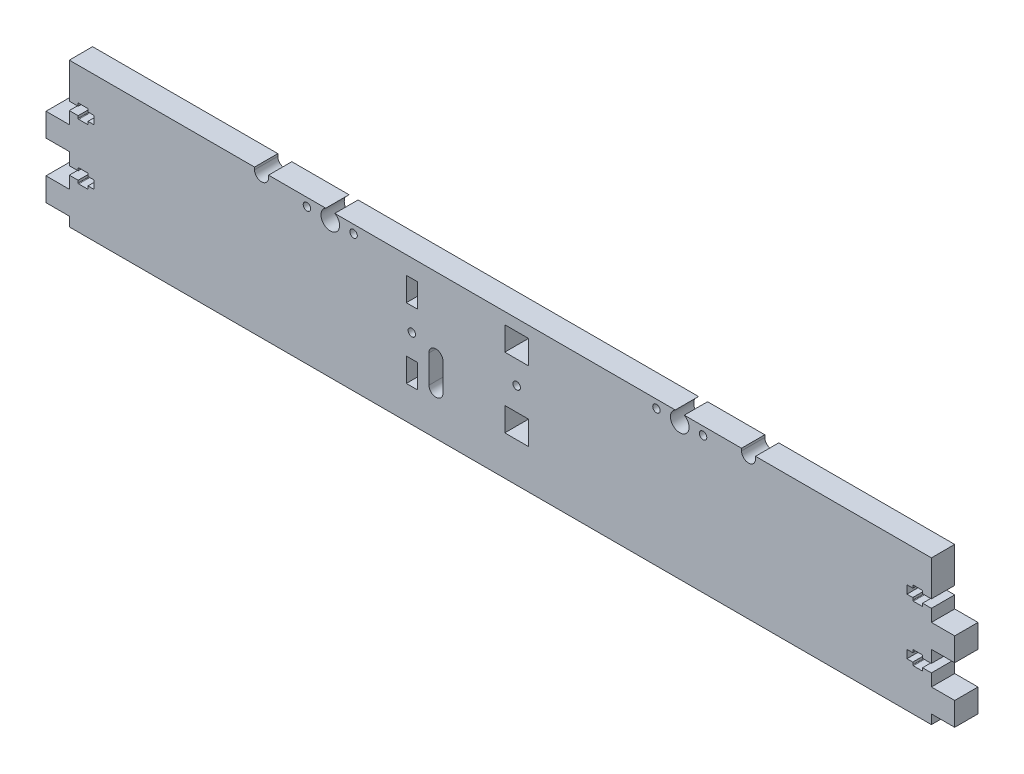
SolidWorks part; units mm, degrees
ref_plane "Front Plane" through (0, 0, 0) normal (0, 0, 1) x (1, 0, 0)
ref_plane "Top Plane" through (0, 0, 0) normal (0, 1, 0) x (1, 0, 0)
ref_plane "Right Plane" through (0, 0, 0) normal (1, 0, 0) x (0, 0, -1)
sketch "Sketch1" plane through (0, 0, 0) normal (0, 0, 1) x (1, 0, 0)
  line L0 (0, 0) -> (-185, 0)
  line L1 (-185, 0) -> (-185, -62) construction
  line L2 (0, -62) -> (-185, -62)
  line L3 (-185, -62) -> (-185, -58)
  line L4 (-185, -58) -> (-195, -58)
  line L5 (-195, -58) -> (-195, -48)
  line L6 (-195, -48) -> (-185, -48)
  line L7 (-185, -48) -> (-185, -34)
  line L8 (-185, -34) -> (-195, -34)
  line L9 (-195, -34) -> (-195, -24)
  line L10 (-195, -24) -> (-185, -24)
  line L11 (0, -62) -> (0, 0)
  line L12 (-185, -24) -> (-185, 0)
  line L13 (-195, -58) -> (-195, -24) construction
  line L14 (-195, -29) -> (-185, -29) construction
  line L15 (-195, -53) -> (-185, -53) construction
  dimension "D3" = 10
  dimension "D1" = 185
  dimension "D2" = 10
  dimension "D4" = 10
  dimension "D5" = 24
  dimension "D6" = 29
  dimension "D7" = 62
extrude "MainBody" add sketch "Sketch1" along normal blind 10
sketch "Sketch3" plane through (0, 0, 10) normal (0, 0, 1) x (1, 0, 0)
  line L0 (-185, -17) -> (-174.5, -17) construction
  line L1 (-185, 0) -> (-185, -24) construction
  line L2 (-185, -18.75) -> (-181.2, -18.75)
  line L3 (-181.2, -18.75) -> (-181.2, -19.75)
  line L4 (-180.95, -20) -> (-177.25, -20)
  line L5 (-177, -19.75) -> (-177, -18.75)
  line L6 (-177, -18.75) -> (-174.5, -18.75)
  line L7 (-174.5, -18.75) -> (-174.5, -15.25)
  line L8 (-181.2, -18.75) -> (-177, -18.75) construction
  line L9 (-195, -24) -> (-195, -34) construction
  line L10 (-181.2, -15.25) -> (-177, -15.25) construction
  line L11 (-177, -15.25) -> (-174.5, -15.25)
  line L12 (-177, -14.25) -> (-177, -15.25)
  line L13 (-180.95, -14) -> (-177.25, -14)
  line L14 (-181.2, -15.25) -> (-181.2, -14.25)
  line L15 (-185, -15.25) -> (-181.2, -15.25)
  line L16 (-185, -18.75) -> (-185, -15.25)
  line L17 (-185, -24) -> (-185, -34) construction
  line L19 (-195, -24) -> (-195, -34) construction
  line L20 (-195, -29) -> (-185, -29) construction
  line L21 (-181.2, -42.75) -> (-177, -42.75) construction
  line L22 (-181.2, -39.25) -> (-177, -39.25) construction
  line L23 (-185, -41) -> (-174.5, -41) construction
  line L24 (-185, -39.25) -> (-185, -42.75)
  line L25 (-185, -42.75) -> (-181.2, -42.75)
  line L26 (-181.2, -42.75) -> (-181.2, -43.75)
  line L27 (-180.95, -44) -> (-177.25, -44)
  line L28 (-177, -43.75) -> (-177, -42.75)
  line L29 (-177, -42.75) -> (-174.5, -42.75)
  line L30 (-174.5, -39.25) -> (-174.5, -42.75)
  line L31 (-177, -39.25) -> (-174.5, -39.25)
  line L32 (-177, -38.25) -> (-177, -39.25)
  line L33 (-180.95, -38) -> (-177.25, -38)
  line L34 (-181.2, -39.25) -> (-181.2, -38.25)
  line L35 (-185, -39.25) -> (-181.2, -39.25)
  line L36 (-181.2, -15.25) -> (-177, -15.25) construction
  arc A0 (-177.25, -20) -> (-177, -19.75) centre (-177.25, -19.75) ccw
  arc A1 (-181.2, -19.75) -> (-180.95, -20) centre (-180.95, -19.75) ccw
  arc A2 (-181.2, -14.25) -> (-180.95, -14) centre (-180.95, -14.25) cw
  arc A3 (-177.25, -14) -> (-177, -14.25) centre (-177.25, -14.25) cw
  arc A4 (-177.25, -44) -> (-177, -43.75) centre (-177.25, -43.75) ccw
  arc A5 (-181.2, -43.75) -> (-180.95, -44) centre (-180.95, -43.75) ccw
  arc A6 (-181.2, -38.25) -> (-180.95, -38) centre (-180.95, -38.25) cw
  arc A7 (-177.25, -38) -> (-177, -38.25) centre (-177.25, -38.25) cw
  point P6 (-195, -29)
  point P15 (-177, -20)
  point P18 (-181.2, -20)
  point P29 (-181.2, -14)
  point P30 (-177, -14)
  point P62 (-177, -44)
  point P63 (-181.2, -44)
  point P64 (-181.2, -38)
  point P65 (-177, -38)
  dimension "D2" = 8
  dimension "D7" = 0.25
  dimension "D1" = 10.5
  dimension "D3" = 1.75
  dimension "D4" = 3
  dimension "D5" = 12
  dimension "D6" = 4.2
extrude "ScrewCutouts" cut sketch "Sketch3" against normal through all
mirror "Mirror1" about plane through (0, 0, 0) normal (1, 0, 0) of "ScrewCutouts", "MainBody"
sketch "Sketch2" plane through (0, 0, 10) normal (0, 0, 1) x (1, 0, 0)
  line L0 (0, 0) -> (0, -62) construction
  line L1 (-185, -62) -> (185, -62) construction
  line L2 (2, 0) -> (2, -62) construction
  line L3 (185, 0) -> (-185, 0) construction
  line L4 (-63, -3.5) -> (-83, -3.5) construction
  line L5 (-73, -7.5) -> (-73, 0.5) construction
  line L6 (77, -7.5) -> (77, 0.5) construction
  line L7 (67, -3.5) -> (87, -3.5) construction
  circle A0 centre (-73, -3.5) radius 4
  circle A1 centre (-83, -3.5) radius 1.6
  circle A2 centre (-63, -3.5) radius 1.6
  circle A3 centre (67, -3.5) radius 1.6
  circle A4 centre (87, -3.5) radius 1.6
  circle A5 centre (77, -3.5) radius 4
  dimension "D1" = 3.2
  dimension "D2" = 8
  dimension "D3" = 10
  dimension "D4" = 3.5
  dimension "D5" = 75
  dimension "D6" = 2
extrude "RodCutouts" cut sketch "Sketch2" against normal through all
sketch "Sketch4" plane through (0, 0, 10) normal (0, 0, 1) x (1, 0, 0)
  line L0 (77, -3.5) -> (-73, -3.5) construction
  line L1 (2, -3.5) -> (2, -62) construction
  line L2 (-185, -62) -> (185, -62) construction
  line L3 (7, -45.1) -> (7, -4.9) construction
  line L4 (75.0635, 0) -> (-71.0635, 0) construction
  line L5 (7, -10) -> (7, -40) construction
  line L6 (1.9, -4.9) -> (12.1, -4.9)
  line L7 (1.9, -4.9) -> (1.9, -15.1)
  line L8 (1.9, -15.1) -> (12.1, -15.1)
  line L9 (12.1, -4.9) -> (12.1, -15.1)
  line L10 (1.9, -4.9) -> (12.1, -15.1) construction
  line L11 (1.9, -15.1) -> (12.1, -4.9) construction
  line L12 (1.9, -34.9) -> (12.1, -34.9)
  line L13 (1.9, -34.9) -> (1.9, -45.1)
  line L14 (1.9, -45.1) -> (12.1, -45.1)
  line L15 (12.1, -34.9) -> (12.1, -45.1)
  line L16 (1.9, -34.9) -> (12.1, -45.1) construction
  line L17 (1.9, -45.1) -> (12.1, -34.9) construction
  circle A0 centre (7, -25) radius 1.6
  point P12 (7, -10)
  point P17 (7, -40)
  dimension "D8" = 3.2
  dimension "D1" = 10.2
  dimension "D2" = 10.2
  dimension "D3" = 10.2
  dimension "D4" = 10.2
  dimension "D5" = 30
  dimension "D6" = 10
  dimension "D7" = 5
extrude "Cut-Extrude3" cut sketch "Sketch4" against normal through all
sketch "Sketch5" plane through (0, 0, 10) normal (0, 0, 1) x (1, 0, 0)
  line L0 (-38, 0) -> (-38, -62) construction
  line L1 (-74.9365, 0) -> (-185, 0) construction
  line L2 (-185, -62) -> (185, -62) construction
  line L3 (-40.35, -17.85) -> (-40.35, -37.65) construction
  line L4 (-40.35, -7.65) -> (-35.65, -7.65)
  line L5 (-40.35, -7.65) -> (-40.35, -17.85)
  line L6 (-40.35, -17.85) -> (-35.65, -17.85)
  line L7 (-35.65, -7.65) -> (-35.65, -17.85)
  line L8 (-40.35, -7.65) -> (-35.65, -17.85) construction
  line L9 (-40.35, -17.85) -> (-35.65, -7.65) construction
  line L10 (-40.35, -37.65) -> (-35.65, -37.65)
  line L11 (-40.35, -37.65) -> (-40.35, -47.85)
  line L12 (-40.35, -47.85) -> (-35.65, -47.85)
  line L13 (-35.65, -37.65) -> (-35.65, -47.85)
  line L14 (-40.35, -37.65) -> (-35.65, -47.85) construction
  line L15 (-40.35, -47.85) -> (-35.65, -37.65) construction
  line L16 (-35.65, -37.65) -> (-35.65, -17.85) construction
  line L17 (-40.35, -27.75) -> (-35.65, -27.75) construction
  line L18 (-73, -3.5) -> (77, -3.5) construction
  line L19 (2, -3.5) -> (2, -62) construction
  line L20 (2, -32.75) -> (-195, -32.75) construction
  line L21 (-195, -24) -> (-195, -34) construction
  circle A0 centre (-38, -27.75) radius 1.6
  point P6 (-38, -12.75)
  point P11 (-38, -42.75)
  dimension "D3" = 10.2
  dimension "D4" = 10.2
  dimension "D5" = 30
  dimension "D6" = 3.2
  dimension "D1" = 4.7
  dimension "D2" = 0
  dimension "D7" = 40
  dimension "D8" = 5
extrude "EndstopHolder" cut sketch "Sketch5" against normal through all
sketch "Sketch6" plane through (0, 0, 10) normal (0, 0, 1) x (1, 0, 0)
  line L0 (-40.35, -37.65) -> (-40.35, -17.85) construction
  line L1 (-42.35, -37.65) -> (-27.65, -37.65) construction
  line L3 (-27.65, -43.65) -> (-27.65, -31.65) construction
  line L4 (-30.65, -43.65) -> (-30.65, -31.65)
  line L5 (-24.65, -43.65) -> (-24.65, -31.65)
  line L6 (-35.65, -37.65) -> (-40.35, -37.65) construction
  line L7 (-35.65, -47.85) -> (-35.65, -37.65) construction
  arc A0 (-30.65, -43.65) -> (-24.65, -43.65) centre (-27.65, -43.65) ccw
  arc A1 (-24.65, -31.65) -> (-30.65, -31.65) centre (-27.65, -31.65) ccw
  point P10 (-27.65, -37.65)
  dimension "D1" = 3
  dimension "D2" = 12
  dimension "D3" = 8
  dimension "D4" = 0
extrude "EndstopWires" cut sketch "Sketch6" against normal through all
sketch "Sketch7" plane through (0, 0, 10) normal (0, 0, 1) x (1, 0, 0)
  line L0 (-73, -3.5) -> (77, -3.5) construction
  line L1 (2, -3.5) -> (2, -62) construction
  line L3 (-102.5, 0) -> (-102.5, -1) construction
  line L4 (-74.9365, 0) -> (-185, 0) construction
  line L5 (-99.5, 0) -> (-99.5, -1)
  line L6 (-105.5, 0) -> (-105.5, -1)
  line L7 (106.5, 0) -> (106.5, -1) construction
  line L8 (103.5, 0) -> (103.5, -1)
  line L9 (109.5, 0) -> (109.5, -1)
  line L10 (-185, -62) -> (185, -62) construction
  arc A0 (-99.5, 0) -> (-105.5, 0) centre (-102.5, 0) ccw
  arc A1 (-105.5, -1) -> (-99.5, -1) centre (-102.5, -1) ccw
  arc A2 (103.5, 0) -> (109.5, 0) centre (106.5, 0) cw
  arc A3 (109.5, -1) -> (103.5, -1) centre (106.5, -1) cw
  point P12 (-102.5, -0.5)
  point P19 (106.5, -0.5)
  dimension "D3" = 3
  dimension "D1" = 1
  dimension "D2" = 104.5
extrude "Cut-Extrude4" cut sketch "Sketch7" against normal through all
equation "\"Y-ROD-SPACING\"=75"
equation "\"D5@Sketch2\"=\"Y-ROD-SPACING\""
equation "\"Y-BED-OFFSET\"=2"
equation "\"D6@Sketch2\"=\"Y-BED-OFFSET\""
equation "\"T-SLOT-NUT-FILLET-RADIUS\"=0.25"
equation "\"D7@Sketch3\"=\"T-SLOT-NUT-FILLET-RADIUS\""
equation "\"T-SLOT-SCREW-SHAFT-RADIUS\"=1.75"
equation "\"D3@Sketch3\"=\"T-SLOT-SCREW-SHAFT-RADIUS\""
equation "\"T-SLOT-SCREW-SHAFT-CUTOUT-LENGTH\"=10.5"
equation "\"D1@Sketch3\"=\"T-SLOT-SCREW-SHAFT-CUTOUT-LENGTH\""
equation "\"T-SLOT-NUT-DEPTH\"=4.2"
equation "\"D6@Sketch3\"=\"T-SLOT-NUT-DEPTH\""
equation "\"T-SLOT-NUT-WIDTH\"=3"
equation "\"D4@Sketch3\"=\"T-SLOT-NUT-WIDTH\""
equation "\"T-SLOT-NUT-END-DISTANCE\"=8"
equation "\"D2@Sketch3\"=\"T-SLOT-NUT-END-DISTANCE\""
equation "\"ACRYLIC-TAB-CUTOUT-SIZE\"=\"ACRYLIC-THICKNESS\"+\"ACRYLIC-TAB-TOLERANCE\"*2"
equation "\"D1@Sketch4\"=\"ACRYLIC-TAB-CUTOUT-SIZE\""
equation "\"D2@Sketch4\"=\"ACRYLIC-TAB-CUTOUT-SIZE\""
equation "\"D3@Sketch4\"=\"ACRYLIC-TAB-CUTOUT-SIZE\""
equation "\"D4@Sketch4\"=\"ACRYLIC-TAB-CUTOUT-SIZE\""
equation "\"ACRYLIC-M3-HOLE\"=3.2"
equation "\"D8@Sketch4\"=\"ACRYLIC-M3-HOLE\""
equation "\"Y-BED-ROD-INSET\"=3.5"
equation "\"D1@Sketch2\"=\"ACRYLIC-M3-HOLE\""
equation "\"D4@Sketch2\"=\"Y-BED-ROD-INSET\""
equation "\"SMOOTHROD-CAP-SCREW-DISTANCE\"=20"
equation "\"D3@Sketch2\"=\"SMOOTHROD-CAP-SCREW-DISTANCE\"/2"
equation "\"ACRYLIC-TAB-WIDTH\"=\"ACRYLIC-THICKNESS\""
equation "\"FRAME-WIDTH-INNER\"=370"
equation "\"D2@Sketch1\"=\"ACRYLIC-TAB-WIDTH\""
equation "\"D3@Sketch1\"=\"ACRYLIC-TAB-WIDTH\""
equation "\"D4@Sketch1\"=\"ACRYLIC-TAB-WIDTH\""
equation "\"D1@Sketch1\"=\"FRAME-WIDTH-INNER\"/2"
equation "\"X-ROD-SPACING\"=45"
equation "\"Z-ROD-SPACING\"=17.5"
equation "\"ACRYLIC-THICKNESS\"=10"
equation "\"ACRYLIC-THICKNESS2\"=4.5"
equation "\"NEMA17-HOLE-SPACING\"=31"
equation "\"NEMA17-CENTRAL-CUTOUT\"=22.5"
equation "\"Z-BRACKET-REACH\"=55"
equation "\"TOP-BRACKET-SPACING\"=40"
equation "\"SMOOTHROD-X-LENGTH\"=350"
equation "\"SMOOTHROD-Y-LENGTH\"=350"
equation "\"SMOOTHROD-Z-LENGTH\"=350"
equation "\"SMOOTHROD-TIGHTENING-HEADROOM\"=1"
equation "\"LEADSCREW-Z-LENGTH\"=300"
equation "\"SCREW-LENGTH-FRAME\"=\"ACRYLIC-THICKNESS\" + 10"
equation "\"SCREW-HEAD-RADIUS\"=6"
equation "\"PRINTED-X-SMOOTHROD-DIAMETER\"=8.2"
equation "\"PRINTED-X-SMOOTHROD-CUTOUT\"=10"
equation "\"PRINTED-X-BASE-HEIGHT\"=10"
equation "\"PRINTED-LM8UU-CUTOUT-SIZE\"=15.25"
equation "\"PRINTED-LM8UU-CUTOUT-LENGTH\"=24.5"
equation "\"PRINTED-X-IDLER-HEIGHT\"=16"
equation "\"PSU-MOUNTING-WIDTH\"=95"
equation "\"PSU-MOUNTING-HEIGHT\"=177"
equation "\"D1@MainBody\"=\"ACRYLIC-THICKNESS\""
equation "\"D1@Sketch5\"=\"ACRYLIC-THICKNESS2\"+\"ACRYLIC-TAB-TOLERANCE\"*2"
equation "\"D3@Sketch5\"=\"ACRYLIC-TAB-CUTOUT-SIZE\""
equation "\"D4@Sketch5\"=\"ACRYLIC-TAB-CUTOUT-SIZE\""
equation "\"D6@Sketch5\"=\"ACRYLIC-M3-HOLE\""
equation "\"Y-BED-SCREW-SPACING\"=209"
equation "\"Y-BED-SCREW-CUTOUT-SLOT-HEIGHT\"=1"
equation "\"Z-ROD-INSET\"=16"
equation "\"Y-BELT-TO-ROD-DISTANCE\"=20"
equation "\"SPOOL-HOLDER-ROD-SPACING\"=150"
equation "\"D1@Sketch7\"=\"Y-BED-SCREW-CUTOUT-SLOT-HEIGHT\""
equation "\"D2@Sketch7\"=\"Y-BED-SCREW-SPACING\"/2"
equation "\"ACRYLIC-TAB-TOLERANCE\"=.1"
equation "\"SCREW-LENGTH-MOTOR\"=\"ACRYLIC-THICKNESS\" + 5"
equation "\"SCREW-LENGTH-EXTRUDER\"=28"
equation "\"ACRYLIC-X-CARRIAGE-WIDTH\"=55"
equation "\"ACRYLIC-X-CARRIAGE-HEIGHT\"=75"
equation "\"ACRYLIC-X-CARRIAGE-LM8UU-CUTOUT-WIDTH\"=24.25"
equation "\"ACRYLIC-X-CARRIAGE-SCREW-SPACING-X\"=15"
equation "\"ACRYLIC-X-CARRIAGE-SCREW-SPACING-Y\"=33"
equation "\"ACRYLIC-X-CARRIAGE-CENTER-TAB-SPACING\"=14"
equation "\"ACRYLIC-X-CARRIAGE-EXTRUDER-OFFSET\"=26"
equation "\"ACRYLIC-X-CARRIAGE-EXTRUDER-ANGLE\"=90"
equation "\"ACRYLIC-X-CARRIAGE-EXTRUDER-SHELF-DEPTH\"=\"ACRYLIC-X-CARRIAGE-EXTRUDER-OFFSET\" + 30"
equation "\"ACRYLIC-X-CARRIAGE-EXTRUDER-BRACE-SPACING\"=23"
equation "\"ACRYLIC-X-CARRIAGE-EXTRUDER-BRACE-TAB-OFFSET\"=20"
equation "\"ACRYLIC-X-CARRIAGE-EXTRUDER-BRACE-HEIGHT\"=35"
equation "\"ACRYLIC-X-CARRIAGE-EXTRUDER-BRACE-SCREW-SPACING\"=22"
